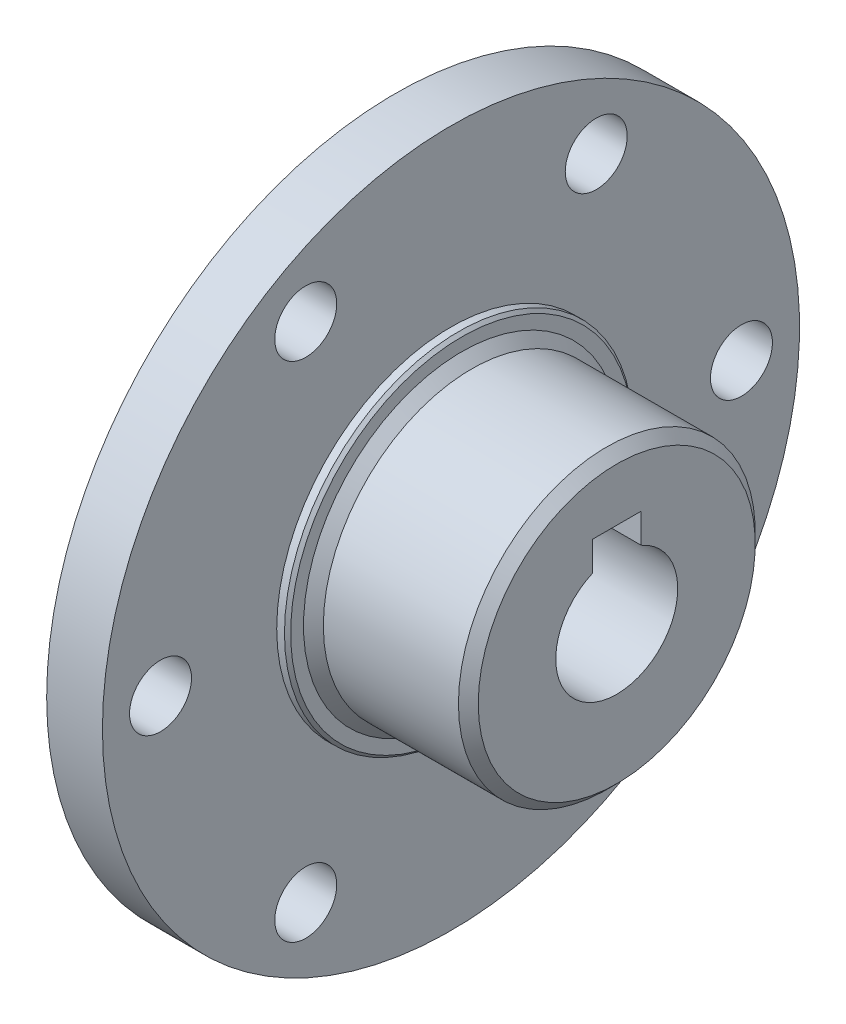
SolidWorks part; units mm, degrees
ref_plane "Front Plane" through (0, 0, 0) normal (0, 0, 1) x (1, 0, 0)
ref_plane "Top Plane" through (0, 0, 0) normal (0, 1, 0) x (1, 0, 0)
ref_plane "Right Plane" through (0, 0, 0) normal (1, 0, 0) x (0, 0, -1)
ref_plane "Plane4" through (0, 0, 0) normal (0, 0, -1) x (-1, 0, 0)
sketch "Sketch1" plane through (0, 0, 0) normal (0, 0, -1) x (-1, 0, 0)
  line L0 (13.0351, 28.575) -> (13.0351, 0)
  line L1 (13.0351, 0) -> (17.6071, 0)
  line L2 (17.6071, 0) -> (17.6071, 28.575)
  line L3 (17.6071, 28.575) -> (13.0351, 28.575)
  line L4 (13.0351, 0) -> (17.6071, 0) construction
revolve "Revolve1" add sketch "Sketch1" angle 360 about L4 reverse direction yes
sketch "Sketch2" plane through (-13.0351, 0, 0) normal (1, 0, 0) x (0, 0, -1)
  circle A0 centre (0, 0) radius 14.2875
extrude "Boss-Extrude1" add sketch "Sketch2" along normal blind 0.889
sketch "Sketch3" plane through (-12.1461, 0, 0) normal (1, 0, 0) x (0, 0, -1)
  circle A0 centre (0, 0) radius 12.1666
extrude "Boss-Extrude2" add sketch "Sketch3" along normal blind 12.7
sketch "Sketch4" plane through (-17.6071, 0, 0) normal (-1, 0, 0) x (0, 0, 1)
  circle A0 centre (0, 0) radius 14.2875
extrude "Boss-Extrude3" add sketch "Sketch4" along normal blind 0.889
sketch "Sketch5" plane through (-18.4961, 0, 0) normal (-1, 0, 0) x (0, 0, 1)
  line L0 (2, 4.5826) -> (2, 7)
  line L1 (2, 7) -> (-2, 7)
  line L2 (-2, 7) -> (-2, 4.5826)
  arc A0 (-2, 4.5826) -> (2, 4.5826) centre (0, 0) cw
extrude "Cut-Extrude1" cut sketch "Sketch5" against normal through all
sketch "Sketch6" plane through (0, 0, 0) normal (0, 0, -1) x (-1, 0, 0)
  line L0 (-0.5539, 5) -> (-0.5539, 0)
  line L1 (-0.5539, 0) -> (18.4961, 0)
  line L2 (18.4961, 0) -> (18.4961, 5)
  line L3 (18.4961, 5) -> (-0.5539, 5)
  line L4 (-0.5539, 0) -> (18.4961, 0) construction
revolve "Cut-Revolve1" cut sketch "Sketch6" angle 360 about L4 reverse direction yes
hole_wizard "#10 Clearance Hole1" positions "Sketch8" profile "Sketch7" hole size "#10" standard "ANSI Inch"
sketch "Sketch8" plane through (-17.6071, 0, 0) normal (-1, 0, 0) x (0, 0, 1)
  point P0 (11.9063, 20.6222)
  point P1 (-11.9062, 20.6222)
  point P2 (-23.8125, 0)
  point P3 (-11.9063, -20.6222)
  point P4 (11.9062, -20.6222)
  point P5 (23.8125, 0)
sketch "Sketch7" plane through (-17.6071, 20.6222, 11.9063) normal (0, 1, 0) x (0, 0, 1)
  line L0 (0, 0) -> (0, 18.161)
  line L1 (0, 18.161) -> (2.54, 18.161)
  line L2 (2.54, 18.161) -> (2.54, 0)
  line L5 (2.54, 0) -> (0, 0)
  line L11 (0, -6.35) -> (0, 107.95) construction
  dimension "Thru Hole Dia." = 5.08
  dimension "Thru Hole Depth" = 18.161
chamfer "Chamfer1" distance 0.254 angle 45 2 edges at (-12.1461, 0, -14.2875) (-18.4961, 0, 14.2875)
chamfer "Chamfer2" distance 0.8128 angle 45 2 edges at (-12.1461, 0, -12.1666) (0.5539, 0, -12.1666)
